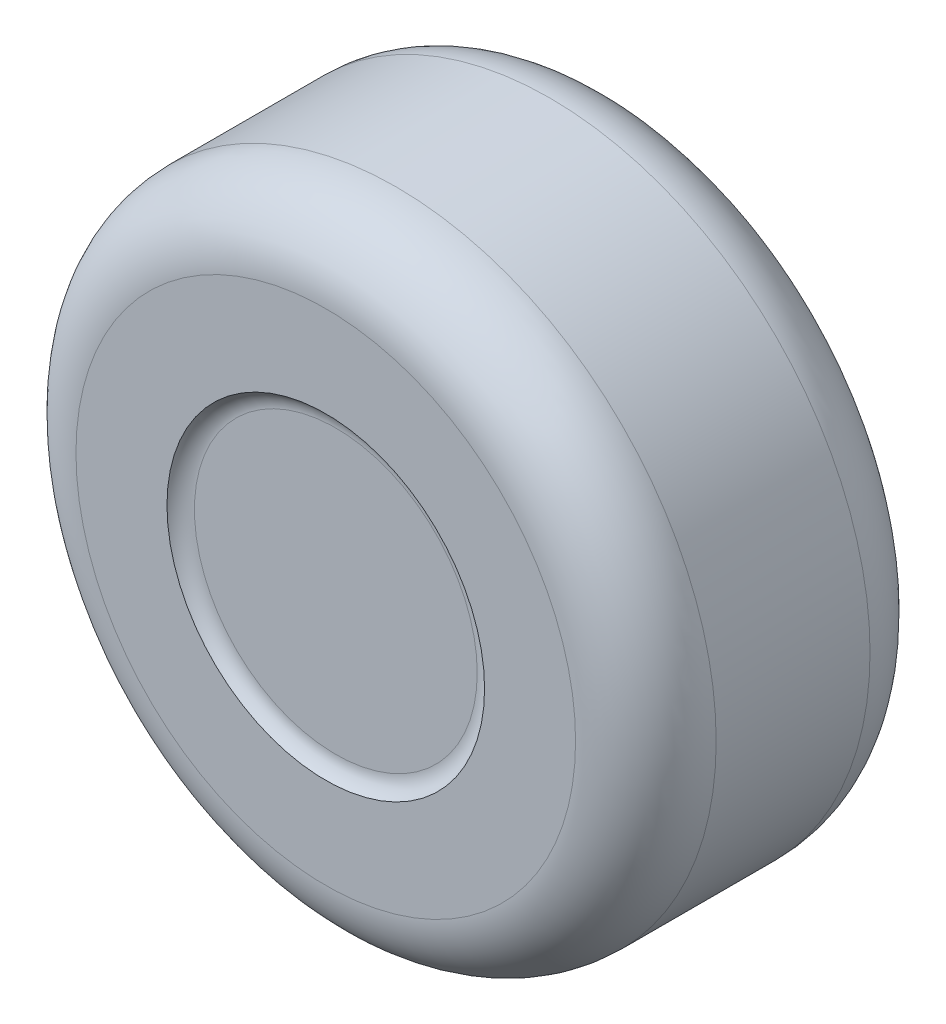
SolidWorks part; units mm, degrees
ref_plane "Alzado" through (0, 0, 0) normal (0, 0, 1) x (1, 0, 0)
ref_plane "Planta" through (0, 0, 0) normal (0, 1, 0) x (1, 0, 0)
ref_plane "Vista lateral" through (0, 0, 0) normal (1, 0, 0) x (0, 0, -1)
sketch "Croquis1" plane through (0, 0, 0) normal (0, 0, 1) x (1, 0, 0)
  circle A0 centre (0, 0) radius 63.75
  dimension "D1" = 127.5
extrude "Saliente-Extruir1" add sketch "Croquis1" along normal mid plane 58.64
sketch "Croquis2" plane through (0, 0, 29.32) normal (0, 0, 1) x (1, 0, 0)
  circle A0 centre (0, 0) radius 31.625
  dimension "D1" = 63.25
extrude "Cortar-Extruir1" cut sketch "Croquis2" against normal blind 2
fillet "Redondeo2" radius 4 1 edges at (31.625, 0, 27.32)
fillet "Redondeo3" radius 14 1 edges at (63.75, 0, 29.32)
sketch "Croquis4" plane through (0, 0, -29.32) normal (0, 0, -1) x (-1, 0, 0)
  circle A0 centre (0, 0) radius 31.625
  dimension "D1" = 63.25
extrude "Cortar-Extruir3" cut sketch "Croquis4" against normal blind 2
sketch "Croquis5" plane through (0, 0, -27.32) normal (0, 0, -1) x (-1, 0, 0)
  circle A0 centre (0, 0) radius 27.12
  dimension "D1" = 54.24
extrude "Cortar-Extruir4" cut sketch "Croquis5" against normal blind 2
fillet "Redondeo4" radius 14 1 edges at (63.75, 0, -29.32)
sketch "Croquis6" plane through (0, 0, -25.32) normal (0, 0, -1) x (-1, 0, 0)
  circle A0 centre (0, 0) radius 4.05
extrude "Cortar-Extruir5" cut sketch "Croquis6" against normal blind 30
fillet "Redondeo5" radius 2 1 edges at (-27.12, 0, -27.32)
fillet "Redondeo6" radius 2 1 edges at (-31.625, 0, -27.32)
